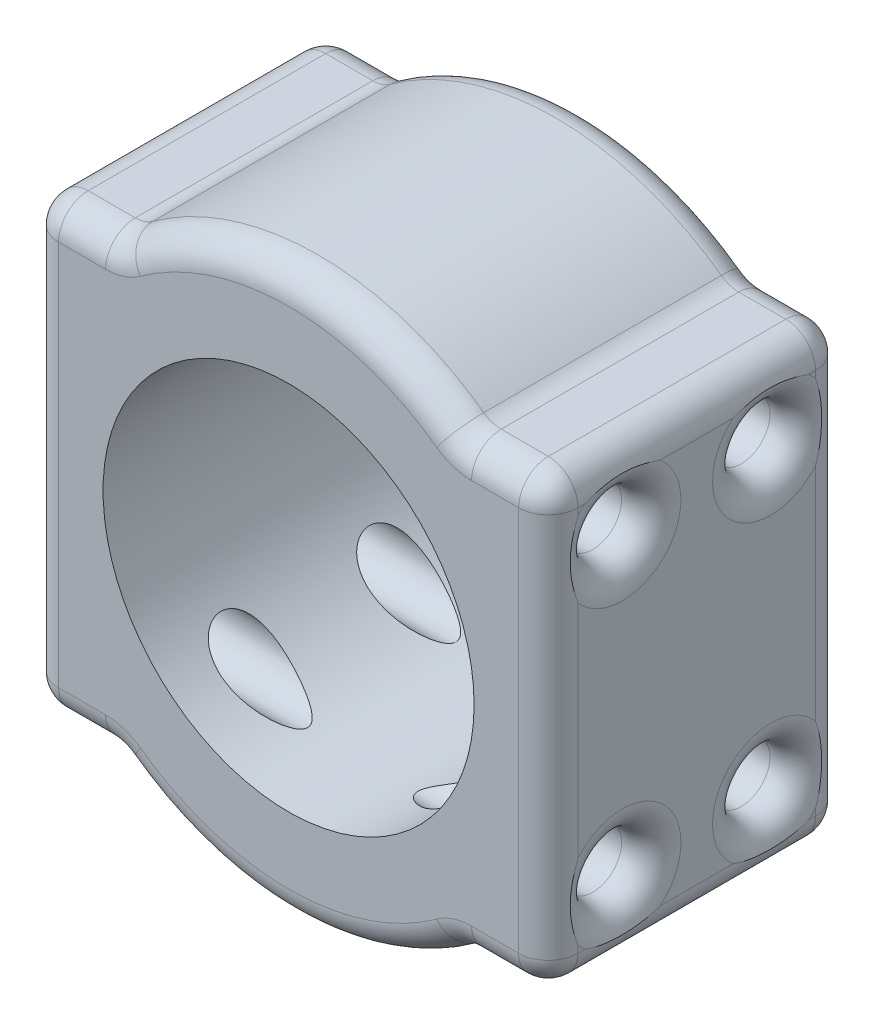
SolidWorks part; units mm, degrees
ref_plane "Front" through (0, 0, 0) normal (0, 0, 1) x (1, 0, 0)
ref_plane "Top" through (0, 0, 0) normal (0, 1, 0) x (1, 0, 0)
ref_plane "Right" through (0, 0, 0) normal (1, 0, 0) x (0, 0, -1)
sketch "Sketch1" plane through (0, 0, 0) normal (0, 0, 1) x (1, 0, 0)
  line L0 (-22.225, 0) -> (0, 0) construction
  line L1 (-19.05, 19.05) -> (-22.225, 19.05)
  line L2 (-19.05, 19.05) -> (-19.05, -19.05)
  line L3 (-19.05, -19.05) -> (-22.225, -19.05)
  line L4 (-22.225, 19.05) -> (-22.225, -19.05)
  line L5 (0, 0) -> (0, 19.05) construction
  line L6 (19.05, -19.05) -> (22.225, -19.05)
  line L7 (22.225, 19.05) -> (22.225, -19.05)
  line L8 (19.05, 19.05) -> (22.225, 19.05)
  line L9 (-19.05, 19.05) -> (0, 19.05)
  line L10 (-19.05, -19.05) -> (0, -19.05)
  line L11 (19.05, -19.05) -> (0, -19.05)
  line L12 (19.05, 19.05) -> (0, 19.05)
  circle A0 centre (0, 0) radius 15.875
  circle A1 centre (0, 0) radius 19.05
  arc A2 (22.225, 9.3971) -> (-22.225, 9.3971) centre (0, 0) ccw
  arc A3 (-22.225, -9.3971) -> (22.225, -9.3971) centre (0, 0) ccw
  dimension "D1" = 31.75
  dimension "D3" = 38.1
  dimension "D7" = 5.08
  dimension "D4" = 3.175
  dimension "D5" = 38.1
  dimension "D6" = 44.45
  dimension "D2" = 3.175
extrude "Boss-Extrude1" add sketch "Sketch1" along normal blind 25.4 contours L1 L4 L3 L2 | A1 L9 L2 | A1 A0 | A1 L2 L10 | A1 L11 L6 L7 L8 L12 | A2 L7 L8 L12 | L12 A2 L9 | A2 L2 L1 L4 | A2 L9 L2 | A3 L11 L6 L7 | L10 A3 L11 | A3 L4 L3 L2 | A3 L2 L10
hole_wizard "#10 (0.1935) Diameter Hole1" positions "Sketch2" profile "Sketch3" hole size "#10" standard "ANSI Inch" end condition through all
sketch "Sketch2" plane through (-22.225, 0, 0) normal (-1, 0, 0) x (0, 0, 1)
  line L0 (12.7, 19.05) -> (12.7, -19.05) construction
  line L1 (25.4, 19.05) -> (0, 19.05) construction
  line L2 (25.4, -19.05) -> (0, -19.05) construction
  line L4 (6.35, 12.7) -> (12.7, 12.7) construction
  line L6 (0, 19.05) -> (0, -19.05) construction
  line L7 (12.7, 0) -> (0, 0) construction
  point P0 (6.35, 12.7)
  point P18 (6.35, -12.7)
  point P19 (19.05, -12.7)
  point P20 (19.05, 12.7)
  dimension "D1" = 6.35
  dimension "D2" = 25.4
sketch "Sketch3" plane through (-22.225, 12.7, 6.35) normal (0, 1, 0) x (0, 0, 1)
  line L0 (0, 0) -> (0, 44.45)
  line L1 (0, 44.45) -> (2.4574, 44.45)
  line L2 (2.4574, 44.45) -> (2.4574, 0)
  line L5 (2.4574, 0) -> (0, 0)
  line L11 (0, -6.35) -> (0, 107.95) construction
  dimension "Thru Hole Dia." = 4.9149
  dimension "Thru Hole Depth" = 44.45
fillet "Fillet2" radius 2.54 32 edges at (-18.5178, -19.05, 25.4) (-18.5178, -19.05, 0) (18.5178, -19.05, 25.4) (18.5178, -19.05, 0) (18.5178, 19.05, 25.4) (18.5178, 19.05, 0) (-18.5178, 19.05, 25.4) (-18.5178, 19.05, 0) (-14.8106, -19.05, 12.7) (0, -24.13, 25.4) (14.8106, -19.05, 12.7) (0, -24.13, 0) (22.225, -19.05, 12.7) (22.225, 0, 25.4) (22.225, 19.05, 12.7) (22.225, 0, 0) (22.225, 12.7, 21.5074) (22.225, -12.7, 21.5074) (22.225, -12.7, 8.8074) (22.225, 12.7, 8.8074) (-22.225, 12.7, 21.5074) (-22.225, 19.05, 12.7) (-22.225, 0, 25.4) (-22.225, -19.05, 12.7) (-22.225, 0, 0) (-22.225, -12.7, 21.5074) (-22.225, -12.7, 8.8074) (-22.225, 12.7, 8.8074) (14.8106, 19.05, 12.7) (0, 24.13, 25.4) (-14.8106, 19.05, 12.7) (0, 24.13, 0)
